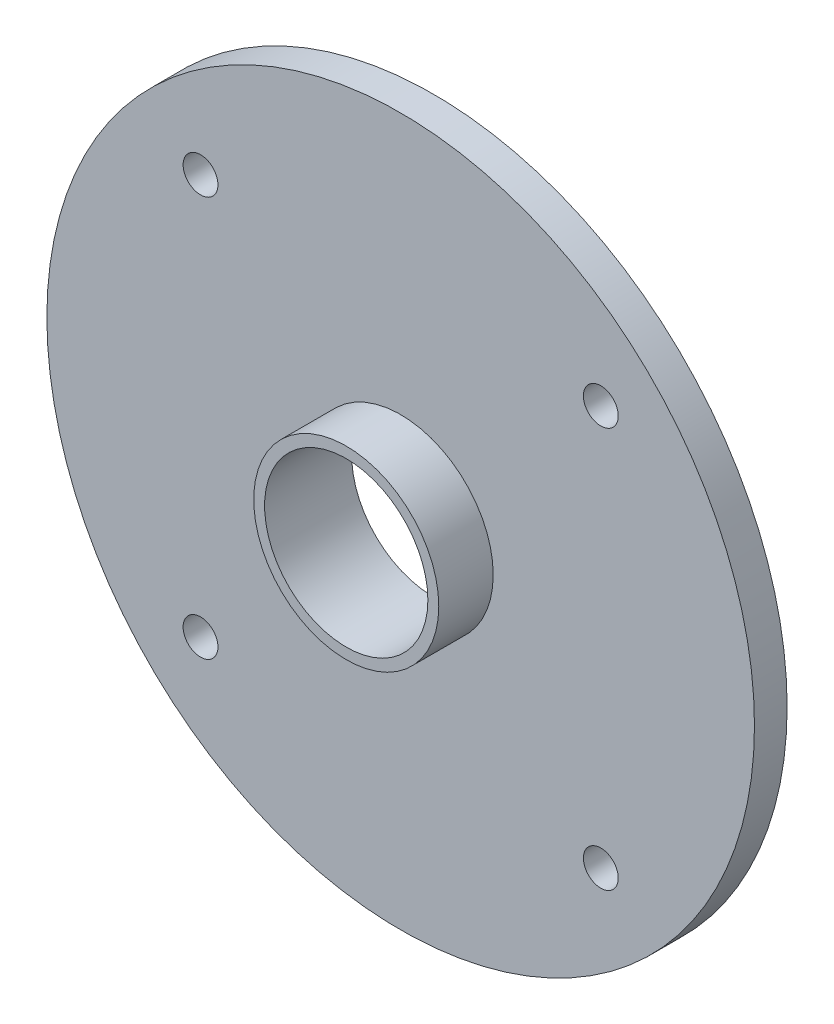
SolidWorks part; units mm, degrees
ref_plane "Спереди" through (0, 0, 0) normal (0, 0, 1) x (1, 0, 0)
ref_plane "Сверху" through (0, 0, 0) normal (0, 1, 0) x (1, 0, 0)
ref_plane "Справа" through (0, 0, 0) normal (1, 0, 0) x (0, 0, -1)
sketch "Эскиз1" plane through (0, 0, 0) normal (0, 0, 1) x (1, 0, 0)
  circle A0 centre (0, 0) radius 32.5
  dimension "D1" = 65
extrude "Бобышка-Вытянуть1" add sketch "Эскиз1" along normal blind 3
sketch "Эскиз2" plane through (0, 0, 3) normal (0, 0, 1) x (1, 0, 0)
  circle A0 centre (0, 0) radius 7.5
  dimension "D1" = 15
extrude "Вырез-Вытянуть1" cut sketch "Эскиз2" against normal through all
sketch "Эскиз3" plane through (0, 0, 3) normal (0, 0, 1) x (1, 0, 0)
  circle A0 centre (0, 0) radius 8.5
  circle A2 centre (0, 0) radius 7.5
  dimension "D1" = 17
  dimension "D2" = 15
extrude "Бобышка-Вытянуть3" add sketch "Эскиз3" along normal blind 5
sketch "Эскиз4" plane through (0, 0, 3) normal (0, 0, 1) x (1, 0, 0)
  line L0 (0, 0) -> (-54.9164, 0) construction
  line L1 (0, 0) -> (-42.4264, 42.4264) construction
  circle A0 centre (0, 0) radius 26 construction
  circle A1 centre (-18.3848, 18.3848) radius 1.6
  circle A2 centre (18.3848, 18.3848) radius 1.6
  circle A3 centre (18.3848, -18.3848) radius 1.6
  circle A4 centre (-18.3848, -18.3848) radius 1.6
  point P16 (0, 0)
  dimension "D1" = 52
  dimension "D3" = 3.2
  dimension "D2" = 45
  dimension "D4" = 4
extrude "Вырез-Вытянуть2" cut sketch "Эскиз4" against normal through all
